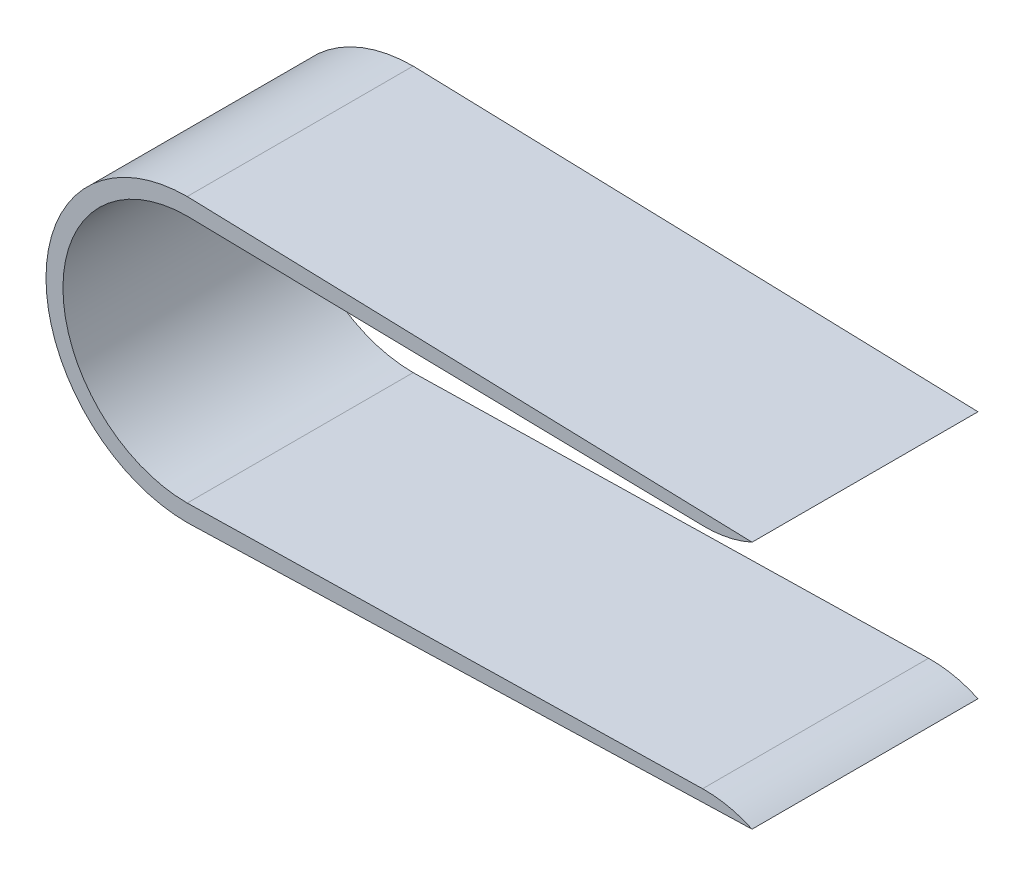
SolidWorks part; units mm, degrees
ref_plane "Front Plane" through (0, 0, 0) normal (0, 0, 1) x (1, 0, 0)
ref_plane "Top Plane" through (0, 0, 0) normal (0, 1, 0) x (1, 0, 0)
ref_plane "Right Plane" through (0, 0, 0) normal (1, 0, 0) x (0, 0, -1)
sketch "Sketch1" plane through (0, 0, 0) normal (0, 0, 1) x (1, 0, 0)
  line L0 (50, 11) -> (50, 10)
  line L1 (0, 12.5) -> (50, 11)
  line L2 (0, 11) -> (50, 10)
  line L3 (50, -11) -> (50, -10)
  line L4 (50, -10) -> (0, -11)
  line L5 (0, -12.5) -> (50, -11)
  arc A0 (0, 11) -> (0, -11) centre (0, 0) ccw
  arc A1 (0, 12.5) -> (0, -12.5) centre (0, 0) ccw
  dimension "D1" = 22
  dimension "D2" = 25
extrude "Boss-Extrude1" add sketch "Sketch1" along normal blind 20
fillet "Fillet1" radius 10 2 edges at (50, -10, 10) (50, 10, 10)
